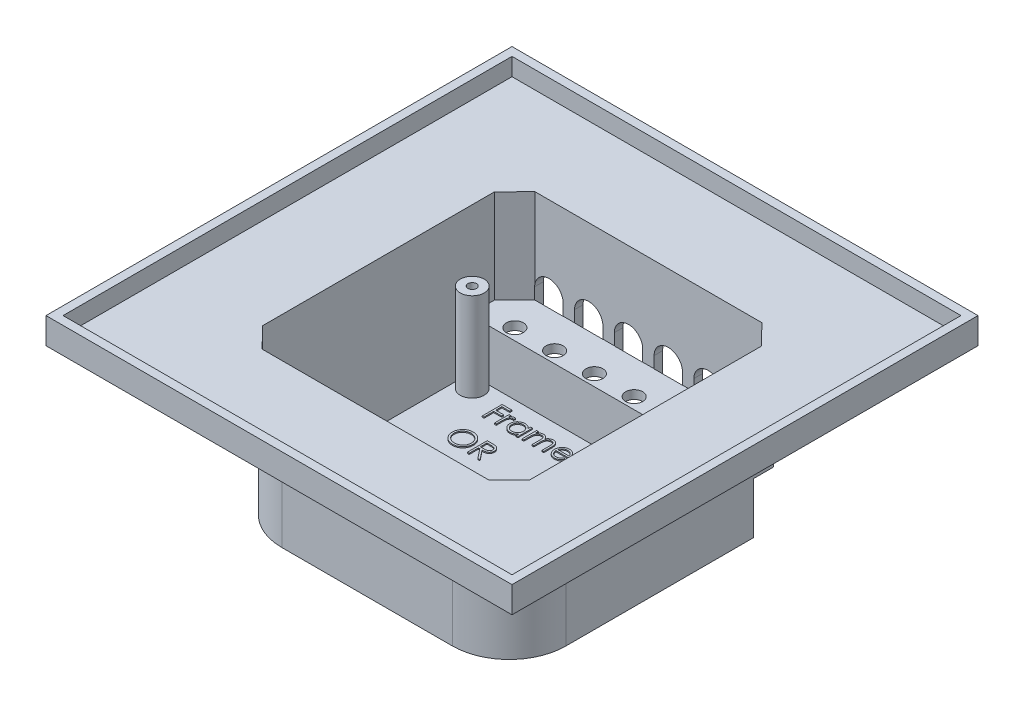
SolidWorks part; units mm, degrees
ref_plane "Front Plane" through (0, 0, 0) normal (0, 0, 1) x (1, 0, 0)
ref_plane "Top Plane" through (0, 0, 0) normal (0, 1, 0) x (1, 0, 0)
ref_plane "Right Plane" through (0, 0, 0) normal (1, 0, 0) x (0, 0, -1)
sketch "Sketch1" plane through (0, 0, 0) normal (0, 1, 0) x (1, 0, 0)
  line L0 (0, 0) -> (0, 25.5) construction
  line L1 (-20.6, 25.5) -> (20.6, 25.5)
  line L4 (25, 21.012) -> (25, -21.012)
  line L5 (-25, 21.012) -> (-25, -21.012)
  line L6 (0, 0) -> (22.8, 23.256) construction
  line L11 (20.6, 25.5) -> (25, 21.012)
  line L12 (0, 25.5) -> (0, -25.5)
  line L13 (-25, 0) -> (25, 0)
  line L14 (-20.6, 25.5) -> (-25, 21.012)
  line L15 (-20.6, -25.5) -> (-25, -21.012)
  line L16 (20.6, -25.5) -> (25, -21.012)
  line L17 (-20.6, -25.5) -> (20.6, -25.5)
  point P0 (0, 0)
  dimension "D1" = 25
  dimension "D2" = 2.2
  dimension "D3" = 4.488
  dimension "D4" = 6.2851
  dimension "D5" = 25.5
  dimension "D6" = 25.5
extrude "Boss-Extrude1" add sketch "Sketch1" along normal blind 25.5 contours L12 L13 L4 L11 L1 | L12 L17 L16 L4 L13 | L15 L17 L12 L13 L5 | L1 L14 L5 L13 L12
sketch "Sketch7" plane through (0, 0, 0) normal (0, -1, 0) x (1, 0, 0)
  line L0 (-20.6, 25.5) -> (-20.6, 15.5) construction
  line L1 (-25, 15.5) -> (-15, 15.5) construction
  line L2 (-25, -21.012) -> (-25, 21.012) construction
  line L3 (-20.6, 25.5) -> (20.6, 25.5) construction
  line L4 (-20.6, 25.5) -> (-25, 21.012) construction
  line L5 (-20.6, 25.5) -> (-25, 21.012)
  line L6 (-20.6, 25.5) -> (-15, 25.5)
  line L7 (-25, 21.012) -> (-25, 15.5)
  line L8 (0, 0) -> (0, 25.5) construction
  line L9 (0, 0) -> (25, 0) construction
  line L10 (25, -21.012) -> (25, 21.012) construction
  line L17 (20.6, 25.5) -> (25, 21.012)
  line L18 (20.6, 25.5) -> (15, 25.5)
  line L19 (25, 21.012) -> (25, 15.5)
  arc A0 (-25, 15.5) -> (-15, 25.5) centre (-15, 15.5) cw
  arc A3 (25, 15.5) -> (15, 25.5) centre (15, 15.5) ccw
  dimension "D1" = 10
  dimension "D2" = 10
extrude "Cut-Extrude2" cut sketch "Sketch7" against normal blind 11.6
sketch "Sketch2" plane through (0, 25.5, 0) normal (0, 1, 0) x (1, 0, 0)
  line L1 (-41, 41) -> (41, 41)
  line L2 (-41, 41) -> (-41, -41)
  line L3 (-41, -41) -> (41, -41)
  line L4 (41, 41) -> (41, -41)
  line L5 (-41, 41) -> (41, -41) construction
  line L6 (-41, -41) -> (41, 41) construction
  point P0 (0, 0)
  dimension "D1" = 82
  dimension "D2" = 82
extrude "Boss-Extrude2" add sketch "Sketch2" along normal blind 4.6
sketch "Sketch4" plane through (0, 0, 0) normal (0, -1, 0) x (1, 0, 0)
  line L0 (25, -21.012) -> (25, 21.012) construction
  line L1 (-25, -21.012) -> (-25, 15.5) construction
  line L2 (-20.6, -25.5) -> (-25, -21.012) construction
  line L3 (-20.6, -25.5) -> (20.6, -25.5) construction
  line L4 (20.6, -25.5) -> (25, -21.012) construction
  line L5 (25, -21.012) -> (25, -17.5)
  line L6 (-25, -21.012) -> (-25, -17.5)
  line L7 (-20.6, -25.5) -> (-25, -21.012)
  line L8 (-20.6, -25.5) -> (20.6, -25.5)
  line L9 (20.6, -25.5) -> (25, -21.012)
  line L10 (-20.6, -25.5) -> (-20.6, -17.5) construction
  line L11 (-25, -17.5) -> (25, -17.5)
  dimension "D1" = 8
extrude "Cut-Extrude1" cut sketch "Sketch4" against normal blind 9 contours L5 L11 L6 L7 L8 L9
shell "Shell1" thickness 1.5
sketch "Sketch5" plane through (0, 27, 0) normal (0, 1, 0) x (1, 0, 0)
  line L0 (0, 24) -> (0, 14) construction
  line L1 (-19.97, 24) -> (19.97, 24) construction
  line L2 (-21, 14) -> (21, 14)
  line L3 (23.5, -20) -> (10, -20) construction
  line L4 (23.5, 20.3994) -> (23.5, -20.3994) construction
  line L5 (-15, -24) -> (15, -24) construction
  circle A0 centre (-21, 14) radius 2.1
  circle A1 centre (21, 14) radius 2.1
  circle A2 centre (-21, 14) radius 0.75
  circle A3 centre (21, 14) radius 0.75
  circle A4 centre (10, -20) radius 2.1
  circle A5 centre (10, -20) radius 0.75
  point P8 (0, 14)
  dimension "D3" = 4.2
  dimension "D4" = 4.2
  dimension "D5" = 1.5
  dimension "D8" = 4.2
  dimension "D9" = 1.5
  dimension "D1" = 10
  dimension "D2" = 42
  dimension "D6" = 13.5
  dimension "D7" = 4
extrude "Boss-Extrude3" add sketch "Sketch5" along normal blind 15.6 from surface
sketch "Sketch8" plane through (0, 10.5, 0) normal (0, 1, 0) x (1, 0, 0)
  line L0 (0, 24) -> (0, 18) construction
  line L1 (-19.97, 24) -> (19.97, 24) construction
  line L2 (20.6108, 18) -> (-20.6108, 18) construction
  line L3 (-3.5, 19.5) -> (-10.5, 19.5) construction
  line L4 (-19.97, 24) -> (19.97, 24) construction
  circle A0 centre (-3.5, 18) radius 1.5
  circle A1 centre (-10.5, 18) radius 1.5
  circle A2 centre (-17.5, 18) radius 1.5
  circle A3 centre (17.5, 18) radius 1.5
  circle A4 centre (10.5, 18) radius 1.5
  circle A5 centre (3.5, 18) radius 1.5
  point P8 (0, 18)
  point P16 (0, 0)
  point P17 (0, 0)
  point P18 (0, 0)
  point P19 (0, 0)
  dimension "D2" = 3.5
  dimension "D3" = 3
  dimension "D5" = 7
  dimension "D6" = 3
  dimension "D7" = 7
  dimension "D8" = 3
  dimension "D9" = 7
  dimension "D10" = 6
  dimension "D1" = 6
  dimension "D4" = 7
  dimension "D11" = 6
extrude "Cut-Extrude3" cut sketch "Sketch8" against normal blind 11.6
sketch "Sketch9" plane through (0, 9, 0) normal (0, -1, 0) x (1, 0, 0)
  line L0 (-17.5, -19.5) -> (-17.5, -25.5) construction
  line L1 (-20.6, -25.5) -> (20.6, -25.5) construction
  line L2 (-13, -27.025) -> (-13, -23.975)
  line L3 (-20, -27.025) -> (-15, -27.025)
  line L4 (-20, -27.025) -> (-20, -23.975)
  line L5 (-20, -23.975) -> (-15, -23.975)
  line L6 (-15, -27.025) -> (-15, -23.975)
  line L7 (-20, -27.025) -> (-15, -23.975) construction
  line L8 (-20, -23.975) -> (-15, -27.025) construction
  line L9 (-13, -27.025) -> (-8, -27.025)
  line L10 (-8, -27.025) -> (-8, -23.975)
  line L11 (-13, -23.975) -> (-8, -23.975)
  line L12 (-6, -27.025) -> (-6, -23.975)
  line L13 (-6, -27.025) -> (-1, -27.025)
  line L14 (-1, -27.025) -> (-1, -23.975)
  line L15 (-6, -23.975) -> (-1, -23.975)
  line L16 (1, -27.025) -> (1, -23.975)
  line L17 (1, -27.025) -> (6, -27.025)
  line L18 (6, -27.025) -> (6, -23.975)
  line L19 (1, -23.975) -> (6, -23.975)
  line L20 (8, -27.025) -> (8, -23.975)
  line L21 (8, -27.025) -> (13, -27.025)
  line L22 (13, -27.025) -> (13, -23.975)
  line L23 (8, -23.975) -> (13, -23.975)
  line L24 (15, -27.025) -> (15, -23.975)
  line L25 (15, -27.025) -> (20, -27.025)
  line L26 (20, -27.025) -> (20, -23.975)
  line L27 (15, -23.975) -> (20, -23.975)
  arc A0 (-18.9142, -17.5) -> (-16.0858, -17.5) centre (-17.5, -18) ccw construction
  dimension "D1" = 5
  dimension "D2" = 3.05
  dimension "D3" = 6
extrude "Cut-Extrude4" cut sketch "Sketch9" against normal blind 6
fillet "Fillet1" radius 2.5 12 edges at (20, 15, -24.7375) (13, 15, -24.75) (6, 15, -24.75) (-1, 15, -24.75) (15, 15, -24.75) (8, 15, -24.75) (1, 15, -24.75) (-6, 15, -24.75) (-13, 15, -24.75) (-8, 15, -24.75) (-15, 15, -24.75) (-20, 15, -24.7375)
sketch "Sketch10" plane through (0, 1.5, 0) normal (0, 1, 0) x (1, 0, 0)
  text T0 "Frame S904 IR\r\nOR\r\nLK-ST13 \r\n\r\n@RBT_DEV"
extrude "Boss-Extrude4" add sketch "Sketch10" along normal blind 0.2
